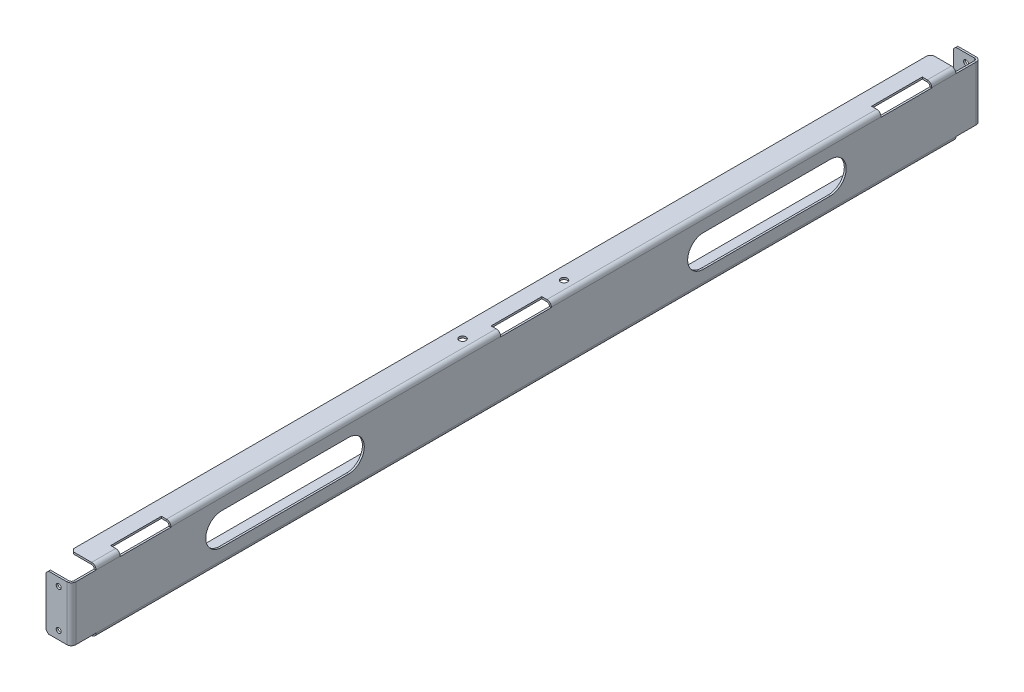
SolidWorks part; units mm, degrees
note: The reader was unsure of these and kept them because the rebuilt part matched: flange length of "Edge-Flange1", "Edge-Flange2".
material "Plain Carbon Steel"
ref_plane "Front Plane" through (0, 0, 0) normal (0, 0, 1) x (1, 0, 0)
ref_plane "Top Plane" through (0, 0, 0) normal (0, 1, 0) x (1, 0, 0)
ref_plane "Right Plane" through (0, 0, 0) normal (1, 0, 0) x (0, 0, -1)
sketch "Sketch1" plane through (0, 0, 0) normal (1, 0, 0) x (0, 0, -1)
  line L1 (0, 0) -> (861.06, 0)
  line L2 (0, 0) -> (0, 63.5)
  line L3 (0, 63.5) -> (861.06, 63.5)
  line L4 (861.06, 0) -> (861.06, 63.5)
  dimension "D1" = 861.06
  dimension "D2" = 63.5
base flange "Base-Flange1" sketch "Sketch1" thickness 1.8974 reverse thickness direction no parameters "D1"=2.54
edge flange "Edge-Flange1" sketch "Sketch10" flange profiles "Sketch10", "Sketch11" flange angle 90 flange length 25.4 flange position material inside bend radius 2.54 thickness 1.8974 relief rectangular parameters "D6"=10, "D8"=0.254
sketch "Sketch10" plane through (-1.8974, 63.5, 0) normal (0, -1, 0) x (0, 0, 1)
  line L2 (-861.06, 0) -> (-861.06, 23.5026)
  line L3 (-861.06, 23.5026) -> (0, 23.5026)
  line L4 (0, 23.5026) -> (0, 0)
  line L5 (0, 0) -> (-861.06, 0) construction
  line L6 (0, 0) -> (-861.06, 0)
sketch "Sketch11" plane through (-1.8974, 0, 0) normal (0, 1, 0) x (0, 0, -1)
  line L0 (861.06, 0) -> (0, 0) construction
  line L1 (861.06, 0) -> (0, 0)
  line L2 (861.06, 0) -> (861.06, 23.5026)
  line L3 (861.06, 23.5026) -> (0, 23.5026)
  line L4 (0, 23.5026) -> (0, 0)
bend "EdgeBend1" bend radius 2.54 bend angle 90 parameters "D5"=1
bend "EdgeBend2" bend radius 2.54 bend angle 90 parameters "D5"=2
ref_plane "Plane1" through (0, 0, -430.53) normal (0, 0, 1) x (1, 0, 0)
sketch "Sketch12" plane through (0, 0, 0) normal (0, 0, 1) x (1, 0, 0)
  line L4 (-1.8974, 59.0626) -> (-1.8974, 4.4374)
  line L5 (-1.8974, 4.4374) -> (0, 4.4374)
  line L6 (0, 4.4374) -> (0, 59.0626)
  line L7 (0, 59.0626) -> (-1.8974, 59.0626)
  line L8 (-1.8974, 59.0626) -> (-1.8974, 4.4374)
  line L9 (-1.8974, 4.4374) -> (0, 4.4374)
  line L10 (0, 4.4374) -> (0, 59.0626)
  line L11 (0, 59.0626) -> (-1.8974, 59.0626)
  dimension "D1" = 0
extrude "Boss-Extrude1" add sketch "Sketch12" along normal blind 24.765
mirror "Mirror1" about plane through (0, 0, -430.53) normal (0, 0, 1) of "Boss-Extrude1"
edge flange "Edge-Flange2" sketch "Sketch23" flange profiles "Sketch23", "Sketch24" flange angle 90 flange length 25.4 flange position material inside bend radius 2.54 thickness 1.8974 relief rectangular parameters "D6"=10, "D8"=0.254
sketch "Sketch23" plane through (-1.8974, 0, 24.765) normal (0, 0, 1) x (0, 1, 0)
  line L2 (4.4374, 0) -> (4.4374, 23.5026)
  line L3 (4.4374, 23.5026) -> (59.0626, 23.5026)
  line L4 (59.0626, 23.5026) -> (59.0626, 0)
  line L7 (59.0626, 0) -> (4.4374, 0) construction
  line L8 (59.0626, 0) -> (4.4374, 0)
sketch "Sketch24" plane through (-1.8974, 0, -885.825) normal (0, 0, -1) x (0, -1, 0)
  line L0 (-59.0626, 0) -> (-4.4374, 0) construction
  line L1 (-59.0626, 0) -> (-4.4374, 0)
  line L2 (-59.0626, 0) -> (-59.0626, 23.5026)
  line L3 (-59.0626, 23.5026) -> (-4.4374, 23.5026)
  line L4 (-4.4374, 23.5026) -> (-4.4374, 0)
bend "EdgeBend3" bend radius 2.54 bend angle 90 parameters "D5"=3
bend "EdgeBend4" bend radius 2.54 bend angle 90 parameters "D5"=4
sketch "Sketch16" plane through (0, 63.5, 0) normal (0, 1, 0) x (1, 0, 0)
  line L0 (0, 861.06) -> (0, 0) construction
  line L1 (0, 24.13) -> (-9.525, 24.13)
  line L2 (0, 24.13) -> (0, 74.93)
  line L3 (0, 74.93) -> (-9.525, 74.93)
  line L4 (-9.525, 24.13) -> (-9.525, 74.93)
  point P6 (0, 430.53)
  dimension "D1" = 406.4
  dimension "D2" = 50.8
  dimension "D3" = 9.525
extrude "Cut-Extrude1" cut sketch "Sketch16" against normal blind 4.7752 normal cut yes
pattern_linear "LPattern1" count 3 spacing 381 along (0, 0, -1) of "Cut-Extrude1"
sketch "Sketch17" plane through (0, 63.5, 0) normal (0, 1, 0) x (1, 0, 0)
  line L0 (-25.4, 0) -> (-25.4, 861.06) construction
  circle A0 centre (-12.7, 481.33) radius 3.3655
  circle A1 centre (-12.7, 379.73) radius 3.3655
  point P8 (-25.4, 430.53)
  dimension "D1" = 6.731
  dimension "D2" = 12.7
  dimension "D3" = 50.8
  dimension "D4" = 101.6
extrude "Cut-Extrude2" cut sketch "Sketch17" against normal blind 2.54
sketch "Sketch18" plane through (0, 0, 0) normal (1, 0, 0) x (0, 0, -1)
  line L0 (125.73, 31.75) -> (252.73, 31.75) construction
  line L1 (125.73, 47.625) -> (252.73, 47.625)
  line L2 (125.73, 15.875) -> (252.73, 15.875)
  line L4 (-20.3276, 59.0626) -> (-20.3276, 4.4374) construction
  line L5 (861.06, 1.8974) -> (0, 1.8974) construction
  arc A0 (125.73, 47.625) -> (125.73, 15.875) centre (125.73, 31.75) ccw
  arc A1 (252.73, 15.875) -> (252.73, 47.625) centre (252.73, 31.75) ccw
  point P2 (189.23, 31.75)
  point P14 (430.53, 1.8974)
  point P15 (-20.3276, 31.75)
  dimension "D1" = 127
  dimension "D2" = 31.75
  dimension "D3" = 177.8
extrude "Cut-Extrude3" cut sketch "Sketch18" against normal blind 2.54 normal cut yes
pattern_linear "LPattern2" count 2 spacing 482.6 along (0, 0, -1) of "Cut-Extrude3"
sketch "Sketch25" plane through (0, 0, 24.765) normal (0, 0, 1) x (1, 0, 0)
  line L0 (0, 59.0626) -> (0, 4.4374) construction
  line L1 (-4.4374, 63.5) -> (-25.4, 63.5) construction
  circle A0 centre (-12.7, 50.8) radius 2.4638
  circle A1 centre (-12.7, 12.7) radius 2.4638
  dimension "D1" = 4.9276
  dimension "D2" = 12.7
  dimension "D3" = 12.7
  dimension "D4" = 38.1
extrude "Cut-Extrude4" cut sketch "Sketch25" against normal through all normal cut yes
chamfer "Chamfer1" distance 2.54 angle 45 8 edges at (-25.4, 4.4374, 23.8163) (-25.4, 0.9487, 0) (-25.4, 59.0626, 23.8163) (-25.4, 62.5513, 0) (-25.4, 62.5513, -861.06) (-25.4, 0.9487, -861.06) (-25.4, 4.4374, -884.8763) (-25.4, 59.0626, -884.8763)
sketch "Bend-Lines1" [suppressed] plane through (0, 0, 0) normal (0, 1, 0) x (1, 0, 0)
sketch "Bounding-Box1" [suppressed] plane through (0, 0, 0) normal (0, 1, 0) x (1, 0, 0)
sheet metal parameters "Sheet-Metal1" thickness 1.8974 parameters "D1"=2.54
flat pattern "Flat-Pattern1" [suppressed]
sketch "Bend-Lines2" plane through (0, 0, 0) normal (0, 1, 0) x (1, 0, 0)
sketch3d "Bounding-Box2" [suppressed]
  line L0 (861.06, 0, 0) -> (0, 0, 0) construction
  line L1 (861.06, 63.5, 0) -> (0, 63.5, 0) construction
  line L2 (861.06, 0, 0) -> (861.06, 63.5, 0) construction
  line L3 (0, 0, 0) -> (0, 63.5, 0) construction
sheet metal parameters "Sheet-Metal2" thickness 1.8974 parameters "D1"=2.54
flat pattern "Flat-Pattern1"
sketch "Bend-Lines2" plane through (0, 0, 0) normal (1, 0, 0) x (0, 0, -1)
  line L0 (0, 1.6974) -> (861.06, 1.6974) construction
  line L1 (861.06, 61.8026) -> (0, 61.8026) construction
  line L2 (0, 1.6974) -> (861.06, 1.6974) construction
  line L3 (861.06, 61.8026) -> (0, 61.8026) construction
sketch3d "Bounding-Box2" [suppressed]
  line L0 (861.06, -22.0053, 0) -> (0, -22.0053, 0) construction
  line L1 (861.06, 85.5053, 0) -> (0, 85.5053, 0) construction
  line L2 (861.06, -22.0053, 0) -> (861.06, 85.5053, 0) construction
  line L3 (0, -22.0053, 0) -> (0, 85.5053, 0) construction
bend of the flat pattern "Flatten-<EdgeBend1>1"
bend of the flat pattern "Flatten-<EdgeBend2>1"
sheet metal parameters "Sheet-Metal3" thickness 1.8974 parameters "D1"=2.54
flat pattern "Flat-Pattern1"
sketch "Bend-Lines2" plane through (0, 0, 0) normal (1, 0, 0) x (0, 0, -1)
  line L0 (0, 1.6974) -> (861.06, 1.6974) construction
  line L1 (861.06, 61.8026) -> (0, 61.8026) construction
  line L2 (0, 1.6974) -> (861.06, 1.6974) construction
  line L3 (861.06, 61.8026) -> (0, 61.8026) construction
sketch3d "Bounding-Box2" [suppressed]
  line L0 (861.06, -22.0053, 0) -> (-24.892, -22.0053, 0) construction
  line L1 (861.06, 85.5053, 0) -> (-24.892, 85.5053, 0) construction
  line L2 (861.06, -22.0053, 0) -> (861.06, 85.5053, 0) construction
  line L3 (-24.892, -22.0053, 0) -> (-24.892, 85.5053, 0) construction
bend of the flat pattern "Flatten-<EdgeBend1>1"
bend of the flat pattern "Flatten-<EdgeBend2>1"
sheet metal parameters "Sheet-Metal5" thickness 1.8974 parameters "D1"=2.54
flat pattern "Flat-Pattern1" [suppressed]
sketch "Bend-Lines2" plane through (0, 0, 0) normal (1, 0, 0) x (0, 0, -1)
  line L0 (0, 1.6974) -> (861.06, 1.6974) construction
  line L1 (24.13, 61.8026) -> (0, 61.8026) construction
  line L2 (0, 1.6974) -> (861.06, 1.6974) construction
  line L3 (24.13, 61.8026) -> (0, 61.8026) construction
  line L4 (861.06, 61.8026) -> (74.93, 61.8026) construction
sketch3d "Bounding-Box2" [suppressed]
  line L0 (885.952, -22.0053, 0) -> (-24.892, -22.0053, 0) construction
  line L1 (885.952, 85.5053, 0) -> (-24.892, 85.5053, 0) construction
  line L2 (885.952, -22.0053, 0) -> (885.952, 85.5053, 0) construction
  line L3 (-24.892, -22.0053, 0) -> (-24.892, 85.5053, 0) construction
bend of the flat pattern "Flatten-<EdgeBend1>1"
bend of the flat pattern "Flatten-<EdgeBend2>1"
bend of the flat pattern "Flatten-<EdgeBend4>2"
bend of the flat pattern "Flatten-<EdgeBend3>2"
sheet metal parameters "Sheet-Metal6" thickness 1.8974 parameters "D1"=2.54
flat pattern "Flat-Pattern1" [suppressed]
sketch "Bend-Lines2" plane through (0, 0, 0) normal (1, 0, 0) x (0, 0, -1)
  line L0 (0, 1.6974) -> (861.06, 1.6974) construction
  line L1 (405.13, 61.8026) -> (74.93, 61.8026) construction
  line L2 (0, 1.6974) -> (861.06, 1.6974) construction
  line L3 (405.13, 61.8026) -> (74.93, 61.8026) construction
  line L4 (24.13, 61.8026) -> (0, 61.8026) construction
  line L5 (861.06, 61.8026) -> (836.93, 61.8026) construction
  line L6 (786.13, 61.8026) -> (455.93, 61.8026) construction
sketch3d "Bounding-Box2" [suppressed]
  line L0 (885.952, -22.0053, 0) -> (-24.892, -22.0053, 0) construction
  line L1 (885.952, 85.5053, 0) -> (-24.892, 85.5053, 0) construction
  line L2 (885.952, -22.0053, 0) -> (885.952, 85.5053, 0) construction
  line L3 (-24.892, -22.0053, 0) -> (-24.892, 85.5053, 0) construction
bend of the flat pattern "Flatten-<EdgeBend1>1"
bend of the flat pattern "Flatten-<EdgeBend2>1"
bend of the flat pattern "Flatten-<EdgeBend4>3"
bend of the flat pattern "Flatten-<EdgeBend3>3"
sheet metal parameters "Sheet-Metal7" thickness 1.8974 parameters "D1"=2.54
flat pattern "Flat-Pattern1" [suppressed]
sketch "Bend-Lines2" plane through (0, 0, 0) normal (1, 0, 0) x (0, 0, -1)
  line L0 (0, 1.6974) -> (861.06, 1.6974) construction
  line L1 (405.13, 61.8026) -> (74.93, 61.8026) construction
  line L2 (0, 1.6974) -> (861.06, 1.6974) construction
  line L3 (405.13, 61.8026) -> (74.93, 61.8026) construction
  line L4 (24.13, 61.8026) -> (0, 61.8026) construction
  line L5 (861.06, 61.8026) -> (836.93, 61.8026) construction
  line L6 (786.13, 61.8026) -> (455.93, 61.8026) construction
sketch3d "Bounding-Box2" [suppressed]
  line L0 (885.952, -22.0053, 0) -> (-24.892, -22.0053, 0) construction
  line L1 (885.952, 85.5053, 0) -> (-24.892, 85.5053, 0) construction
  line L2 (885.952, -22.0053, 0) -> (885.952, 85.5053, 0) construction
  line L3 (-24.892, -22.0053, 0) -> (-24.892, 85.5053, 0) construction
bend of the flat pattern "Flatten-<EdgeBend1>1"
bend of the flat pattern "Flatten-<EdgeBend2>1"
bend of the flat pattern "Flatten-<EdgeBend4>4"
bend of the flat pattern "Flatten-<EdgeBend3>4"
sheet metal parameters "Sheet-Metal8" thickness 1.8974 parameters "D1"=2.54
flat pattern "Flat-Pattern1" [suppressed]
sketch "Bend-Lines2" plane through (0, 0, 0) normal (1, 0, 0) x (0, 0, -1)
  line L0 (0, 1.6974) -> (861.06, 1.6974) construction
  line L1 (405.13, 61.8026) -> (74.93, 61.8026) construction
  line L2 (0, 1.6974) -> (861.06, 1.6974) construction
  line L3 (405.13, 61.8026) -> (74.93, 61.8026) construction
  line L4 (24.13, 61.8026) -> (0, 61.8026) construction
  line L5 (861.06, 61.8026) -> (836.93, 61.8026) construction
  line L6 (786.13, 61.8026) -> (455.93, 61.8026) construction
sketch3d "Bounding-Box2" [suppressed]
  line L0 (885.952, -22.0053, 0) -> (-24.892, -22.0053, 0) construction
  line L1 (885.952, 85.5053, 0) -> (-24.892, 85.5053, 0) construction
  line L2 (885.952, -22.0053, 0) -> (885.952, 85.5053, 0) construction
  line L3 (-24.892, -22.0053, 0) -> (-24.892, 85.5053, 0) construction
bend of the flat pattern "Flatten-<EdgeBend1>1"
bend of the flat pattern "Flatten-<EdgeBend2>1"
bend of the flat pattern "Flatten-<EdgeBend4>5"
bend of the flat pattern "Flatten-<EdgeBend3>5"
sheet metal parameters "Sheet-Metal9" thickness 1.8974 parameters "D1"=2.54
flat pattern "Flat-Pattern1"
sketch "Bend-Lines2" plane through (0, 0, 0) normal (1, 0, 0) x (0, 0, -1)
  line L0 (0, 1.6974) -> (861.06, 1.6974) construction
  line L1 (405.13, 61.8026) -> (74.93, 61.8026) construction
  line L2 (0, 1.6974) -> (861.06, 1.6974) construction
  line L3 (405.13, 61.8026) -> (74.93, 61.8026) construction
  line L4 (24.13, 61.8026) -> (0, 61.8026) construction
  line L5 (861.06, 61.8026) -> (836.93, 61.8026) construction
  line L6 (786.13, 61.8026) -> (455.93, 61.8026) construction
  line L7 (884.1276, 4.4374) -> (884.1276, 59.0626) construction
  line L8 (-23.0676, 59.0626) -> (-23.0676, 4.4374) construction
  line L9 (884.1276, 4.4374) -> (884.1276, 59.0626) construction
  line L10 (-23.0676, 59.0626) -> (-23.0676, 4.4374) construction
sketch3d "Bounding-Box2" [suppressed]
  line L0 (907.8303, -22.0053, 0) -> (-46.7703, -22.0053, 0) construction
  line L1 (907.8303, 85.5053, 0) -> (-46.7703, 85.5053, 0) construction
  line L2 (907.8303, -22.0053, 0) -> (907.8303, 85.5053, 0) construction
  line L3 (-46.7703, -22.0053, 0) -> (-46.7703, 85.5053, 0) construction
bend of the flat pattern "Flatten-<EdgeBend1>1"
bend of the flat pattern "Flatten-<EdgeBend2>1"
bend of the flat pattern "Flatten-<EdgeBend4>6"
bend of the flat pattern "Flatten-<EdgeBend3>6"
sheet metal parameters "Sheet-Metal10" thickness 1.8974 parameters "D1"=2.54
flat pattern "Flat-Pattern1"
sketch "Bend-Lines2" plane through (0, 0, 0) normal (1, 0, 0) x (0, 0, -1)
  line L0 (0, 1.6974) -> (861.06, 1.6974) construction
  line L1 (861.06, 61.8026) -> (0, 61.8026) construction
  line L2 (0, 1.6974) -> (861.06, 1.6974) construction
  line L3 (861.06, 61.8026) -> (0, 61.8026) construction
sketch3d "Bounding-Box2" [suppressed]
  line L0 (885.952, -22.0053, 0) -> (-24.892, -22.0053, 0) construction
  line L1 (885.952, 85.5053, 0) -> (-24.892, 85.5053, 0) construction
  line L2 (885.952, -22.0053, 0) -> (885.952, 85.5053, 0) construction
  line L3 (-24.892, -22.0053, 0) -> (-24.892, 85.5053, 0) construction
bend of the flat pattern "Flatten-<EdgeBend1>1"
bend of the flat pattern "Flatten-<EdgeBend2>1"
sheet metal parameters "Sheet-Metal11" thickness 1.8974 parameters "D1"=2.54
flat pattern "Flat-Pattern1"
sketch "Bend-Lines2" plane through (0, 0, 0) normal (1, 0, 0) x (0, 0, -1)
  line L0 (0, 1.6974) -> (861.06, 1.6974) construction
  line L1 (861.06, 61.8026) -> (0, 61.8026) construction
  line L2 (0, 1.6974) -> (861.06, 1.6974) construction
  line L3 (861.06, 61.8026) -> (0, 61.8026) construction
  line L4 (884.1276, 4.4374) -> (884.1276, 59.0626) construction
  line L5 (-23.0676, 59.0626) -> (-23.0676, 4.4374) construction
  line L6 (884.1276, 4.4374) -> (884.1276, 59.0626) construction
  line L7 (-23.0676, 59.0626) -> (-23.0676, 4.4374) construction
sketch3d "Bounding-Box2" [suppressed]
  line L0 (907.8303, -22.0053, 0) -> (-46.7703, -22.0053, 0) construction
  line L1 (907.8303, 85.5053, 0) -> (-46.7703, 85.5053, 0) construction
  line L2 (907.8303, -22.0053, 0) -> (907.8303, 85.5053, 0) construction
  line L3 (-46.7703, -22.0053, 0) -> (-46.7703, 85.5053, 0) construction
bend of the flat pattern "Flatten-<EdgeBend1>1"
bend of the flat pattern "Flatten-<EdgeBend2>1"
bend of the flat pattern "Flatten-<EdgeBend3>1"
bend of the flat pattern "Flatten-<EdgeBend4>1"
sheet metal parameters "Sheet-Metal12" thickness 1.8974 parameters "D1"=2.54
flat pattern "Flat-Pattern1"
sketch "Bend-Lines2" plane through (0, 0, 0) normal (1, 0, 0) x (0, 0, -1)
  line L0 (0, 1.6974) -> (861.06, 1.6974) construction
  line L1 (405.13, 61.8026) -> (74.93, 61.8026) construction
  line L2 (0, 1.6974) -> (861.06, 1.6974) construction
  line L3 (405.13, 61.8026) -> (74.93, 61.8026) construction
  line L4 (24.13, 61.8026) -> (0, 61.8026) construction
  line L5 (861.06, 61.8026) -> (836.93, 61.8026) construction
  line L6 (786.13, 61.8026) -> (455.93, 61.8026) construction
  line L7 (884.1276, 4.4374) -> (884.1276, 59.0626) construction
  line L8 (-23.0676, 59.0626) -> (-23.0676, 4.4374) construction
  line L9 (884.1276, 4.4374) -> (884.1276, 59.0626) construction
  line L10 (-23.0676, 59.0626) -> (-23.0676, 4.4374) construction
sketch3d "Bounding-Box2" [suppressed]
  line L0 (907.8303, -22.0053, 0) -> (-46.7703, -22.0053, 0) construction
  line L1 (907.8303, 85.5053, 0) -> (-46.7703, 85.5053, 0) construction
  line L2 (907.8303, -22.0053, 0) -> (907.8303, 85.5053, 0) construction
  line L3 (-46.7703, -22.0053, 0) -> (-46.7703, 85.5053, 0) construction
bend of the flat pattern "Flatten-<EdgeBend1>1"
bend of the flat pattern "Flatten-<EdgeBend2>1"
bend of the flat pattern "Flatten-<EdgeBend4>6"
bend of the flat pattern "Flatten-<EdgeBend3>6"
